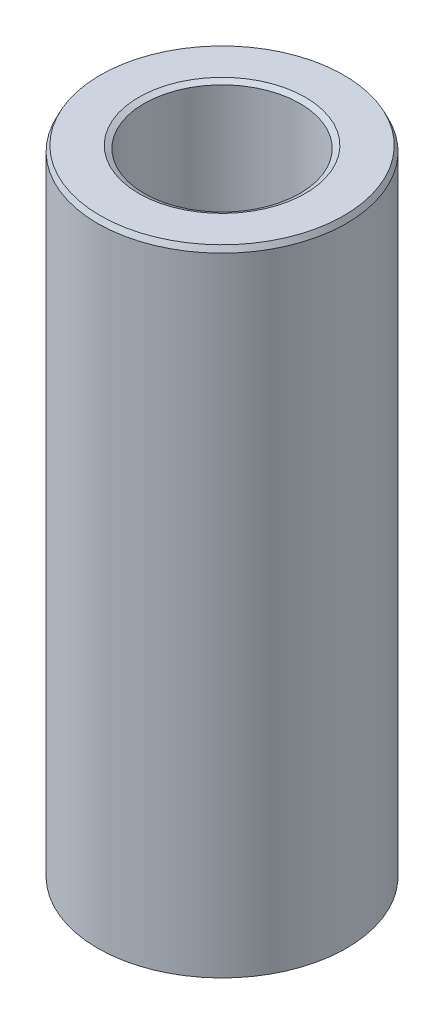
SolidWorks part; units mm, degrees
ref_plane "Front Plane" through (0, 0, 0) normal (0, 0, 1) x (1, 0, 0)
ref_plane "Top Plane" through (0, 0, 0) normal (0, 1, 0) x (1, 0, 0)
ref_plane "Right Plane" through (0, 0, 0) normal (1, 0, 0) x (0, 0, -1)
sketch "Sketch1" plane through (0, 0, 0) normal (0, 1, 0) x (1, 0, 0)
  circle A0 centre (0, 0) radius 32.5
  dimension "SLEEVE_OD" = 65
extrude "Boss-Extrude1" add sketch "Sketch1" along normal blind 166.044
sketch "Sketch2" plane through (0, 0, 0) normal (0, 1, 0) x (1, 0, 0)
  circle A0 centre (0, 0) radius 20.3544
  dimension "BORE_D" = 40.7089
extrude "Cut-Extrude1" cut sketch "Sketch2" along normal through all
chamfer "Chamfer1" distance 1.412 angle 26.321 4 edges at (0, 166.044, 20.3544) (0, 0, 20.3544) (0, 0, 32.5) (0, 166.044, 32.5) first distance on face at (0, 166.044, 20.3544) first distance on face at (0, 0, 20.3544) first distance on face at (0, 166.044, 32.5)
